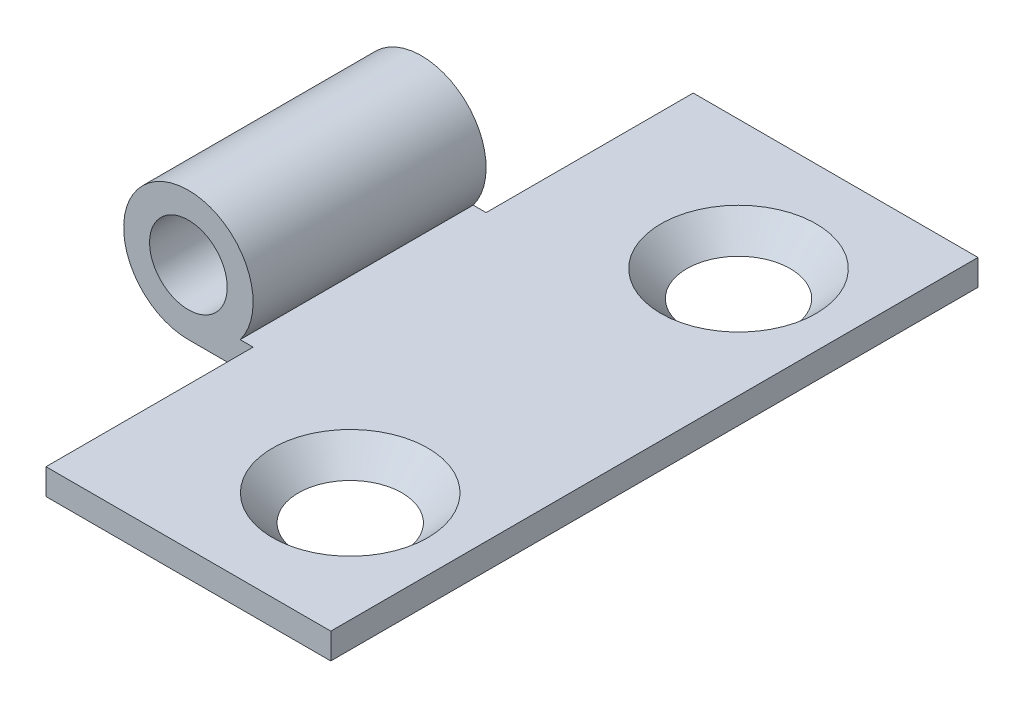
SolidWorks part; units mm, degrees
ref_plane "前视基准面" through (0, 0, 0) normal (0, 0, 1) x (1, 0, 0)
ref_plane "上视基准面" through (0, 0, 0) normal (0, 1, 0) x (1, 0, 0)
ref_plane "右视基准面" through (0, 0, 0) normal (1, 0, 0) x (0, 0, -1)
sketch "草图1" plane through (0, 0, 0) normal (0, 0, 1) x (1, 0, 0)
  line L0 (0, -2.5) -> (13.5, -2.5)
  line L1 (13.5, -2.5) -> (13.5, -1.5)
  line L2 (13.5, -1.5) -> (2, -1.5)
  arc A0 (2, -1.5) -> (0, -2.5) centre (0, 0) ccw
  circle A1 centre (0, 0) radius 1.5
  dimension "D3" = 5
  dimension "D4" = 3
  dimension "D1" = 1
  dimension "D2" = 13.5
extrude "凸台-拉伸1" add sketch "草图1" along normal blind 25
sketch "草图2" plane through (0, -2.5, 0) normal (0, -1, 0) x (1, 0, 0)
  line L0 (-2.5, 12.5) -> (13.5, 12.5) construction
  line L1 (-2.5, 25) -> (-2.5, 0) construction
  line L2 (13.5, 25) -> (13.5, 0) construction
  line L3 (-2.5, 0) -> (-2.5, 8)
  line L8 (-2.5, 25) -> (2.5, 25)
  line L9 (-2.5, 25) -> (-2.5, 17)
  line L10 (-2.5, 17) -> (2.5, 17)
  line L11 (2.5, 25) -> (2.5, 17)
  line L12 (-2.5, 0) -> (2.5, 0)
  line L13 (2.5, 0) -> (2.5, 8)
  line L14 (-2.5, 8) -> (2.5, 8)
  circle A0 centre (9.25, 20) radius 2
  circle A1 centre (9.25, 5) radius 2
  dimension "D1" = 4
  dimension "D2" = 9.25
  dimension "D3" = 15
  dimension "D4" = 5
  dimension "D5" = 8
extrude "切除-拉伸1" cut sketch "草图2" against normal through all
chamfer "倒角1" distance 1 angle 45 2 edges at (11.25, -1.5, 20) (11.25, -1.5, 5)
